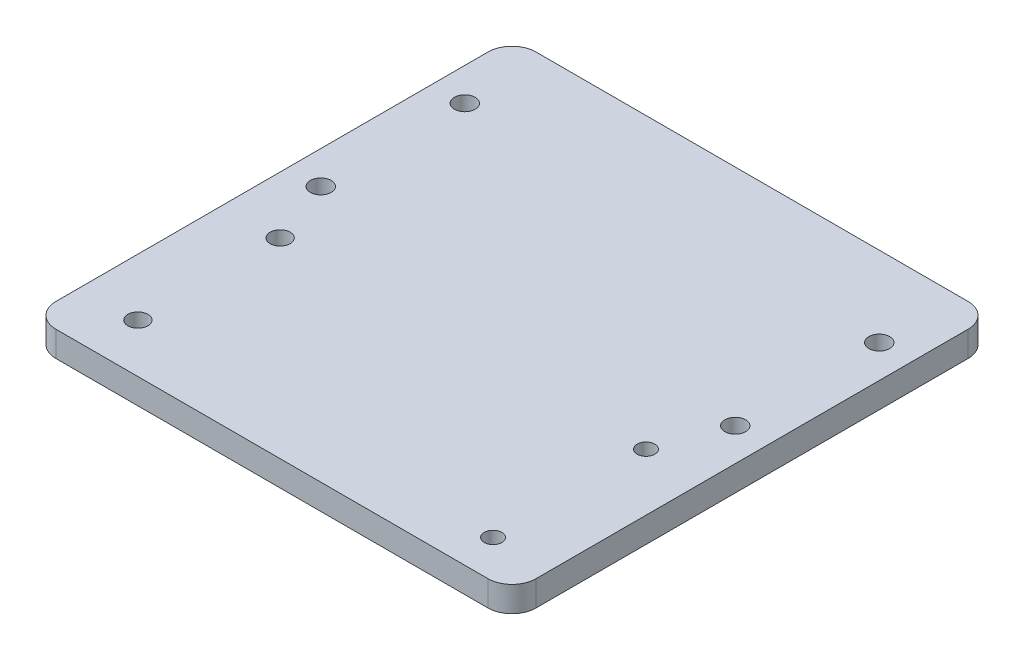
SolidWorks part; units mm, degrees
ref_plane "Front Plane" through (0, 0, 0) normal (0, 0, 1) x (1, 0, 0)
ref_plane "Top Plane" through (0, 0, 0) normal (0, 1, 0) x (1, 0, 0)
ref_plane "Right Plane" through (0, 0, 0) normal (1, 0, 0) x (0, 0, -1)
sketch "Sketch1" plane through (0, 0, 0) normal (0, 1, 0) x (1, 0, 0)
  line L1 (-30, 30) -> (30, 30)
  line L2 (-30, 30) -> (-30, -30)
  line L3 (-30, -30) -> (30, -30)
  line L4 (30, 30) -> (30, -30)
  line L5 (-30, 30) -> (30, -30) construction
  line L6 (-30, -30) -> (30, 30) construction
  point P0 (0, 0)
  dimension "D1" = 60
  dimension "D2" = 60
extrude "Boss-Extrude1" add sketch "Sketch1" along normal blind 3.175
sketch "Sketch2" plane through (0, 3.175, 0) normal (0, 1, 0) x (1, 0, 0)
  line L0 (0, 30) -> (0, -30) construction
  line L1 (30, 30) -> (-30, 30) construction
  line L2 (-30, -30) -> (30, -30) construction
  line L3 (-30, 30) -> (-30, -30) construction
  circle A0 centre (-25.9, 20) radius 1.3
  circle A1 centre (-25.9, 2) radius 1.3
  circle A2 centre (25.9, 2) radius 1.3
  circle A3 centre (25.9, 20) radius 1.3
  point P11 (-24.6, 20)
  point P17 (24.6, 20)
  dimension "D1" = 2.6
  dimension "D2" = 18
  dimension "D3" = 5.4
  dimension "D4" = 10
extrude "Cut-Extrude1" cut sketch "Sketch2" against normal up to surface (3.175 mm away) up to face at (0, 0, 0)
fillet "Fillet1" radius 3 4 edges at (-30, 1.5875, 30) (30, 1.5875, 30) (30, 1.5875, -30) (-30, 1.5875, -30)
sketch "Sketch3" plane through (0, 3.175, 0) normal (0, 1, 0) x (1, 0, 0)
  line L0 (-30, 0) -> (30, 0) construction
  line L1 (-22.865, -6.11) -> (22.855, -6.11) construction
  line L2 (-22.865, -6.11) -> (-22.865, -23.89) construction
  line L3 (-22.865, -23.89) -> (22.855, -25.22) construction
  line L4 (22.855, -6.11) -> (22.855, -25.22) construction
  line L5 (-30, 27) -> (-30, -27) construction
  line L6 (30, -27) -> (30, 27) construction
  circle A0 centre (-22.865, -6.11) radius 1.25
  circle A1 centre (22.855, -6.11) radius 1.1
  circle A2 centre (22.855, -25.22) radius 1.1
  circle A3 centre (-22.865, -23.89) radius 1.25
  dimension "D1" = 2.5
  dimension "D6" = 2.2
  dimension "D2" = 45.72
  dimension "D3" = 17.78
  dimension "D4" = 19.11
  dimension "D5" = 45.72
extrude "Cut-Extrude2" cut sketch "Sketch3" against normal up to surface (3.175 mm away) up to face at (25.9, 0, -18.7)
